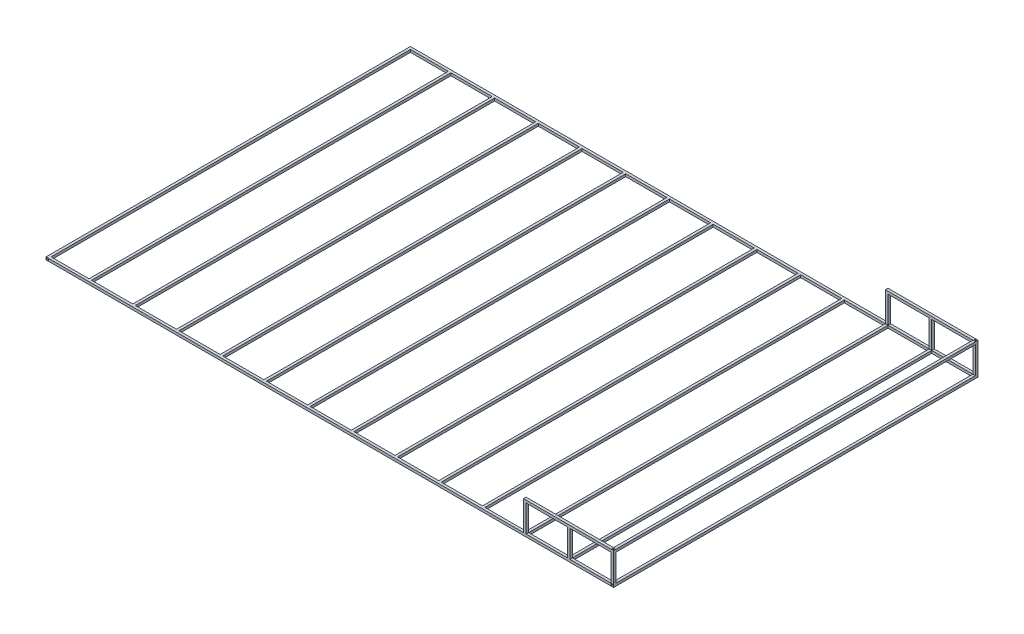
SolidWorks part; units mm, degrees
ref_plane "Front Plane" through (0, 0, 0) normal (0, 0, 1) x (1, 0, 0)
ref_plane "Top Plane" through (0, 0, 0) normal (0, 1, 0) x (1, 0, 0)
ref_plane "Right Plane" through (0, 0, 0) normal (1, 0, 0) x (0, 0, -1)
sketch "Sketch1" plane through (0, 0, 0) normal (0, 1, 0) x (1, 0, 0)
  line L1 (0, 0) -> (-8410, 0)
  line L2 (0, 0) -> (0, 5400)
  line L3 (0, 5400) -> (-8410, 5400)
  line L4 (-8410, 0) -> (-8410, 5400)
  point P5 (0, 0)
  point P6 (0, 0)
  dimension "D1" = 8410
  dimension "D2" = 5400
sketch "Sketch2" plane through (0, 0, 0) normal (0, 0, 1) x (1, 0, 0)
  line L0 (-35.4, 5.24) -> (-35.4, 32.86)
  line L1 (0, 0) -> (-38.1, 0)
  line L2 (0, 0) -> (0, 38.1)
  line L3 (0, 38.1) -> (-38.1, 38.1)
  line L4 (-38.1, 0) -> (-38.1, 38.1)
  line L5 (-5.24, 35.4) -> (-32.86, 35.4)
  line L6 (-2.7, 5.24) -> (-2.7, 32.86)
  line L7 (-5.24, 2.7) -> (-32.86, 2.7)
  line L8 (-35.4, 2.7) -> (-35.4, 35.4) construction
  line L9 (-2.7, 2.7) -> (-35.4, 2.7) construction
  line L10 (-2.7, 35.4) -> (-35.4, 35.4) construction
  line L11 (-2.7, 2.7) -> (-2.7, 35.4) construction
  arc A0 (-35.4, 5.24) -> (-32.86, 2.7) centre (-32.86, 5.24) ccw
  arc A1 (-35.4, 32.86) -> (-32.86, 35.4) centre (-32.86, 32.86) cw
  arc A2 (-5.24, 35.4) -> (-2.7, 32.86) centre (-5.24, 32.86) cw
  arc A3 (-2.7, 5.24) -> (-5.24, 2.7) centre (-5.24, 5.24) cw
  dimension "D4" = 2.54
  dimension "D1" = 38.1
  dimension "D2" = 38.1
  dimension "D3" = 2.7
extrude "Boss-Extrude1" add sketch "Sketch2" against normal up to vertex (5400 mm away) up to point (0, 0, -5400)
sketch "Sketch3" plane through (-38.1, 0, 0) normal (-1, 0, 0) x (0, 0, 1)
  line L0 (0, 0) -> (-5400, 0) construction
  line L1 (-5400, 38.1) -> (-5361.9, 38.1)
  line L2 (-5400, 38.1) -> (-5400, 0)
  line L3 (-5400, 0) -> (-5361.9, 0)
  line L4 (-5361.9, 38.1) -> (-5361.9, 0)
  line L5 (-5364.6, 32.86) -> (-5364.6, 5.24)
  line L6 (-5394.76, 2.7) -> (-5367.14, 2.7)
  line L7 (-5397.3, 32.86) -> (-5397.3, 5.24)
  line L8 (-5394.76, 35.4) -> (-5367.14, 35.4)
  line L9 (-5364.6, 35.4) -> (-5364.6, 2.7) construction
  line L10 (-5397.3, 2.7) -> (-5364.6, 2.7) construction
  line L11 (-5397.3, 35.4) -> (-5397.3, 2.7) construction
  line L12 (-5397.3, 35.4) -> (-5364.6, 35.4) construction
  line L14 (-2700, 254.2441) -> (-2700, -216.1397) construction
  line L15 (-5400, 38.1) -> (0, 38.1) construction
  line L16 (-2.7, 32.86) -> (-2.7, 5.24)
  line L17 (0, 38.1) -> (0, 0)
  line L18 (-5.24, 2.7) -> (-32.86, 2.7)
  line L19 (-5.24, 35.4) -> (-32.86, 35.4)
  line L20 (0, 38.1) -> (-38.1, 38.1)
  line L21 (0, 0) -> (-38.1, 0)
  line L22 (-35.4, 32.86) -> (-35.4, 5.24)
  line L23 (-38.1, 38.1) -> (-38.1, 0)
  arc A0 (-5364.6, 5.24) -> (-5367.14, 2.7) centre (-5367.14, 5.24) cw
  arc A1 (-5394.76, 2.7) -> (-5397.3, 5.24) centre (-5394.76, 5.24) cw
  arc A2 (-5397.3, 32.86) -> (-5394.76, 35.4) centre (-5394.76, 32.86) cw
  arc A3 (-5364.6, 32.86) -> (-5367.14, 35.4) centre (-5367.14, 32.86) ccw
  arc A4 (-2.7, 32.86) -> (-5.24, 35.4) centre (-5.24, 32.86) ccw
  arc A5 (-5.24, 2.7) -> (-2.7, 5.24) centre (-5.24, 5.24) ccw
  arc A6 (-35.4, 32.86) -> (-32.86, 35.4) centre (-32.86, 32.86) cw
  arc A7 (-35.4, 5.24) -> (-32.86, 2.7) centre (-32.86, 5.24) ccw
  point P25 (-2700, 38.1)
  dimension "D3" = 2.54
  dimension "D1" = 38.1
  dimension "D2" = 2.7
extrude "Boss-Extrude2" add sketch "Sketch3" along normal blind 8333.8
pattern_linear "LPattern1" count 2 spacing 8371.9 along (-1, 0, 0) of "Boss-Extrude1"
sketch "Sketch4" plane through (0, 0, -5361.9) normal (0, 0, 1) x (1, 0, 0)
  line L0 (-8371.9, 38.1) -> (-38.1, 38.1) construction
  line L1 (-647.7, 38.1) -> (-685.8, 38.1)
  line L2 (-647.7, 38.1) -> (-647.7, 0)
  line L3 (-647.7, 0) -> (-685.8, 0)
  line L4 (-685.8, 38.1) -> (-685.8, 0)
  line L5 (-8371.9, 0) -> (-38.1, 0) construction
  line L6 (-38.1, 0) -> (-38.1, 38.1) construction
  line L7 (-1295.4, 38.1) -> (-1295.4, 0)
  line L8 (-1333.5, 38.1) -> (-1333.5, 0)
  line L9 (-1295.4, 38.1) -> (-1333.5, 38.1)
  line L10 (-1295.4, 0) -> (-1333.5, 0)
  line L11 (-1943.1, 38.1) -> (-1943.1, 0)
  line L12 (-1981.2, 38.1) -> (-1981.2, 0)
  line L13 (-1943.1, 38.1) -> (-1981.2, 38.1)
  line L14 (-1943.1, 0) -> (-1981.2, 0)
  line L15 (-2590.8, 38.1) -> (-2590.8, 0)
  line L16 (-2628.9, 38.1) -> (-2628.9, 0)
  line L17 (-2590.8, 38.1) -> (-2628.9, 38.1)
  line L18 (-2590.8, 0) -> (-2628.9, 0)
  line L19 (-3238.5, 38.1) -> (-3238.5, 0)
  line L20 (-3276.6, 38.1) -> (-3276.6, 0)
  line L21 (-3238.5, 38.1) -> (-3276.6, 38.1)
  line L22 (-3238.5, 0) -> (-3276.6, 0)
  line L23 (-3886.2, 38.1) -> (-3886.2, 0)
  line L24 (-3924.3, 38.1) -> (-3924.3, 0)
  line L25 (-3886.2, 38.1) -> (-3924.3, 38.1)
  line L26 (-3886.2, 0) -> (-3924.3, 0)
  line L27 (-4533.9, 38.1) -> (-4533.9, 0)
  line L28 (-4572, 38.1) -> (-4572, 0)
  line L29 (-4533.9, 38.1) -> (-4572, 38.1)
  line L30 (-4533.9, 0) -> (-4572, 0)
  line L31 (-5181.6, 38.1) -> (-5181.6, 0)
  line L32 (-5219.7, 38.1) -> (-5219.7, 0)
  line L33 (-5181.6, 38.1) -> (-5219.7, 38.1)
  line L34 (-5181.6, 0) -> (-5219.7, 0)
  line L35 (-5829.3, 38.1) -> (-5829.3, 0)
  line L36 (-5867.4, 38.1) -> (-5867.4, 0)
  line L37 (-5829.3, 38.1) -> (-5867.4, 38.1)
  line L38 (-5829.3, 0) -> (-5867.4, 0)
  line L39 (-6477, 38.1) -> (-6477, 0)
  line L40 (-6515.1, 38.1) -> (-6515.1, 0)
  line L41 (-6477, 38.1) -> (-6515.1, 38.1)
  line L42 (-6477, 0) -> (-6515.1, 0)
  line L43 (-7124.7, 38.1) -> (-7124.7, 0)
  line L44 (-7162.8, 38.1) -> (-7162.8, 0)
  line L45 (-7124.7, 38.1) -> (-7162.8, 38.1)
  line L46 (-7124.7, 0) -> (-7162.8, 0)
  line L47 (-7772.4, 38.1) -> (-7772.4, 0)
  line L48 (-7810.5, 38.1) -> (-7810.5, 0)
  line L49 (-7772.4, 38.1) -> (-7810.5, 38.1)
  line L50 (-7772.4, 0) -> (-7810.5, 0)
  line L55 (-8420.1, 38.1) -> (-8458.2, 38.1) [skipped]
  line L56 (-8420.1, 0) -> (-8458.2, 0) [skipped]
  line L57 (-8458.2, 38.1) -> (-8458.2, 0) [skipped]
  line L58 (-8420.1, 38.1) -> (-8420.1, 0) [skipped]
  dimension "D1" = 38.1
  dimension "D2" = 609.6
  dimension "D4" = 609.6
  dimension "D3" = 13
extrude "Boss-Extrude3" add sketch "Sketch4" along normal up to surface (5323.8 mm away) up to face at (-4205, 19.05, -38.1)
sketch "Sketch5" plane through (0, 38.1, 0) normal (0, 1, 0) x (1, 0, 0)
  line L0 (-32.86, 35.4) -> (-5.24, 35.4)
  line L1 (-38.1, 38.1) -> (0, 38.1)
  line L2 (-38.1, 38.1) -> (-38.1, 0)
  line L3 (-38.1, 0) -> (0, 0)
  line L4 (0, 38.1) -> (0, 0)
  line L5 (-2.7, 32.86) -> (-2.7, 5.24)
  line L6 (-32.86, 2.7) -> (-5.24, 2.7)
  line L7 (-35.4, 32.86) -> (-35.4, 5.24)
  line L8 (-35.4, 35.4) -> (-2.7, 35.4) construction
  line L9 (-35.4, 35.4) -> (-35.4, 2.7) construction
  line L10 (-35.4, 2.7) -> (-2.7, 2.7) construction
  line L11 (-2.7, 35.4) -> (-2.7, 2.7) construction
  line L12 (0, 5400) -> (0, 0) construction
  line L13 (0, 2700) -> (-153.8549, 2700) construction
  line L14 (-35.4, 5367.14) -> (-35.4, 5394.76)
  line L15 (-32.86, 5397.3) -> (-5.24, 5397.3)
  line L16 (-2.7, 5367.14) -> (-2.7, 5394.76)
  line L17 (0, 5361.9) -> (0, 5400)
  line L18 (-38.1, 5400) -> (0, 5400)
  line L19 (-38.1, 5361.9) -> (-38.1, 5400)
  line L20 (-38.1, 5361.9) -> (0, 5361.9)
  line L21 (-32.86, 5364.6) -> (-5.24, 5364.6)
  line L22 (-680.56, 35.4) -> (-652.94, 35.4)
  line L23 (-683.1, 32.86) -> (-683.1, 5.24)
  line L24 (-680.56, 2.7) -> (-652.94, 2.7)
  line L25 (-650.4, 32.86) -> (-650.4, 5.24)
  line L26 (-685.8, 38.1) -> (-647.7, 38.1)
  line L27 (-647.7, 38.1) -> (-647.7, 0)
  line L28 (-685.8, 0) -> (-647.7, 0)
  line L29 (-685.8, 38.1) -> (-685.8, 0)
  line L30 (-685.8, 5361.9) -> (-685.8, 5400)
  line L31 (-683.1, 5367.14) -> (-683.1, 5394.76)
  line L32 (-680.56, 5364.6) -> (-652.94, 5364.6)
  line L33 (-685.8, 5361.9) -> (-647.7, 5361.9)
  line L34 (-650.4, 5367.14) -> (-650.4, 5394.76)
  line L35 (-647.7, 5361.9) -> (-647.7, 5400)
  line L36 (-685.8, 5400) -> (-647.7, 5400)
  line L37 (-680.56, 5397.3) -> (-652.94, 5397.3)
  line L38 (-1298.1, 32.86) -> (-1298.1, 5.24)
  line L39 (-1328.26, 2.7) -> (-1300.64, 2.7)
  line L40 (-1333.5, 0) -> (-1295.4, 0)
  line L41 (-1295.4, 38.1) -> (-1295.4, 0)
  line L42 (-1333.5, 38.1) -> (-1295.4, 38.1)
  line L43 (-1328.26, 35.4) -> (-1300.64, 35.4)
  line L44 (-1333.5, 38.1) -> (-1333.5, 0)
  line L45 (-1330.8, 32.86) -> (-1330.8, 5.24)
  line L46 (-1298.1, 5367.14) -> (-1298.1, 5394.76)
  line L47 (-1333.5, 5361.9) -> (-1295.4, 5361.9)
  line L48 (-1295.4, 5361.9) -> (-1295.4, 5400)
  line L49 (-1328.26, 5397.3) -> (-1300.64, 5397.3)
  line L50 (-1333.5, 5400) -> (-1295.4, 5400)
  line L51 (-1330.8, 5367.14) -> (-1330.8, 5394.76)
  line L52 (-1333.5, 5361.9) -> (-1333.5, 5400)
  line L53 (-1328.26, 5364.6) -> (-1300.64, 5364.6)
  line L54 (-1945.8, 32.86) -> (-1945.8, 5.24)
  line L55 (-1975.96, 2.7) -> (-1948.34, 2.7)
  line L56 (-1981.2, 0) -> (-1943.1, 0)
  line L57 (-1943.1, 38.1) -> (-1943.1, 0)
  line L58 (-1981.2, 38.1) -> (-1943.1, 38.1)
  line L59 (-1975.96, 35.4) -> (-1948.34, 35.4)
  line L60 (-1981.2, 38.1) -> (-1981.2, 0)
  line L61 (-1978.5, 32.86) -> (-1978.5, 5.24)
  line L62 (-1945.8, 5367.14) -> (-1945.8, 5394.76)
  line L63 (-1981.2, 5361.9) -> (-1943.1, 5361.9)
  line L64 (-1943.1, 5361.9) -> (-1943.1, 5400)
  line L65 (-1975.96, 5397.3) -> (-1948.34, 5397.3)
  line L66 (-1981.2, 5400) -> (-1943.1, 5400)
  line L67 (-1978.5, 5367.14) -> (-1978.5, 5394.76)
  line L68 (-1981.2, 5361.9) -> (-1981.2, 5400)
  line L69 (-1975.96, 5364.6) -> (-1948.34, 5364.6)
  line L70 (-2593.5, 32.86) -> (-2593.5, 5.24)
  line L71 (-2623.66, 2.7) -> (-2596.04, 2.7)
  line L72 (-2628.9, 0) -> (-2590.8, 0)
  line L73 (-2590.8, 38.1) -> (-2590.8, 0)
  line L74 (-2628.9, 38.1) -> (-2590.8, 38.1)
  line L75 (-2623.66, 35.4) -> (-2596.04, 35.4)
  line L76 (-2628.9, 38.1) -> (-2628.9, 0)
  line L77 (-2626.2, 32.86) -> (-2626.2, 5.24)
  line L78 (-2593.5, 5367.14) -> (-2593.5, 5394.76)
  line L79 (-2628.9, 5361.9) -> (-2590.8, 5361.9)
  line L80 (-2590.8, 5361.9) -> (-2590.8, 5400)
  line L81 (-2623.66, 5397.3) -> (-2596.04, 5397.3)
  line L82 (-2628.9, 5400) -> (-2590.8, 5400)
  line L83 (-2626.2, 5367.14) -> (-2626.2, 5394.76)
  line L84 (-2628.9, 5361.9) -> (-2628.9, 5400)
  line L85 (-2623.66, 5364.6) -> (-2596.04, 5364.6)
  line L86 (-3241.2, 32.86) -> (-3241.2, 5.24)
  line L87 (-3271.36, 2.7) -> (-3243.74, 2.7)
  line L88 (-3276.6, 0) -> (-3238.5, 0)
  line L89 (-3238.5, 38.1) -> (-3238.5, 0)
  line L90 (-3276.6, 38.1) -> (-3238.5, 38.1)
  line L91 (-3271.36, 35.4) -> (-3243.74, 35.4)
  line L92 (-3276.6, 38.1) -> (-3276.6, 0)
  line L93 (-3273.9, 32.86) -> (-3273.9, 5.24)
  line L94 (-3241.2, 5367.14) -> (-3241.2, 5394.76)
  line L95 (-3276.6, 5361.9) -> (-3238.5, 5361.9)
  line L96 (-3238.5, 5361.9) -> (-3238.5, 5400)
  line L97 (-3271.36, 5397.3) -> (-3243.74, 5397.3)
  line L98 (-3276.6, 5400) -> (-3238.5, 5400)
  line L99 (-3273.9, 5367.14) -> (-3273.9, 5394.76)
  line L100 (-3276.6, 5361.9) -> (-3276.6, 5400)
  line L101 (-3271.36, 5364.6) -> (-3243.74, 5364.6)
  line L102 (-3888.9, 32.86) -> (-3888.9, 5.24)
  line L103 (-3919.06, 2.7) -> (-3891.44, 2.7)
  line L104 (-3924.3, 0) -> (-3886.2, 0)
  line L105 (-3886.2, 38.1) -> (-3886.2, 0)
  line L106 (-3924.3, 38.1) -> (-3886.2, 38.1)
  line L107 (-3919.06, 35.4) -> (-3891.44, 35.4)
  line L108 (-3924.3, 38.1) -> (-3924.3, 0)
  line L109 (-3921.6, 32.86) -> (-3921.6, 5.24)
  line L110 (-3888.9, 5367.14) -> (-3888.9, 5394.76)
  line L111 (-3924.3, 5361.9) -> (-3886.2, 5361.9)
  line L112 (-3886.2, 5361.9) -> (-3886.2, 5400)
  line L113 (-3919.06, 5397.3) -> (-3891.44, 5397.3)
  line L114 (-3924.3, 5400) -> (-3886.2, 5400)
  line L115 (-3921.6, 5367.14) -> (-3921.6, 5394.76)
  line L116 (-3924.3, 5361.9) -> (-3924.3, 5400)
  line L117 (-3919.06, 5364.6) -> (-3891.44, 5364.6)
  line L118 (-647.7, 38.1) -> (-647.7, 5361.9) construction
  line L119 (-647.7, 5361.9) -> (-38.1, 5361.9) construction
  line L120 (-1333.5, 38.1) -> (-1333.5, 5361.9) construction
  line L121 (-1943.1, 5361.9) -> (-1333.5, 5361.9) construction
  arc A0 (-32.86, 35.4) -> (-35.4, 32.86) centre (-32.86, 32.86) ccw
  arc A1 (-32.86, 2.7) -> (-35.4, 5.24) centre (-32.86, 5.24) cw
  arc A2 (-2.7, 5.24) -> (-5.24, 2.7) centre (-5.24, 5.24) cw
  arc A3 (-5.24, 35.4) -> (-2.7, 32.86) centre (-5.24, 32.86) cw
  arc A4 (-5.24, 5364.6) -> (-2.7, 5367.14) centre (-5.24, 5367.14) ccw
  arc A5 (-2.7, 5394.76) -> (-5.24, 5397.3) centre (-5.24, 5394.76) ccw
  arc A6 (-32.86, 5397.3) -> (-35.4, 5394.76) centre (-32.86, 5394.76) ccw
  arc A7 (-32.86, 5364.6) -> (-35.4, 5367.14) centre (-32.86, 5367.14) cw
  arc A8 (-680.56, 35.4) -> (-683.1, 32.86) centre (-680.56, 32.86) ccw
  arc A9 (-680.56, 2.7) -> (-683.1, 5.24) centre (-680.56, 5.24) cw
  arc A10 (-650.4, 5.24) -> (-652.94, 2.7) centre (-652.94, 5.24) cw
  arc A11 (-652.94, 35.4) -> (-650.4, 32.86) centre (-652.94, 32.86) cw
  arc A12 (-680.56, 5364.6) -> (-683.1, 5367.14) centre (-680.56, 5367.14) cw
  arc A13 (-652.94, 5364.6) -> (-650.4, 5367.14) centre (-652.94, 5367.14) ccw
  arc A14 (-650.4, 5394.76) -> (-652.94, 5397.3) centre (-652.94, 5394.76) ccw
  arc A15 (-680.56, 5397.3) -> (-683.1, 5394.76) centre (-680.56, 5394.76) ccw
  arc A16 (-1298.1, 5.24) -> (-1300.64, 2.7) centre (-1300.64, 5.24) cw
  arc A17 (-1300.64, 35.4) -> (-1298.1, 32.86) centre (-1300.64, 32.86) cw
  arc A18 (-1328.26, 35.4) -> (-1330.8, 32.86) centre (-1328.26, 32.86) ccw
  arc A19 (-1328.26, 2.7) -> (-1330.8, 5.24) centre (-1328.26, 5.24) cw
  arc A20 (-1300.64, 5364.6) -> (-1298.1, 5367.14) centre (-1300.64, 5367.14) ccw
  arc A21 (-1298.1, 5394.76) -> (-1300.64, 5397.3) centre (-1300.64, 5394.76) ccw
  arc A22 (-1328.26, 5397.3) -> (-1330.8, 5394.76) centre (-1328.26, 5394.76) ccw
  arc A23 (-1328.26, 5364.6) -> (-1330.8, 5367.14) centre (-1328.26, 5367.14) cw
  arc A24 (-1945.8, 5.24) -> (-1948.34, 2.7) centre (-1948.34, 5.24) cw
  arc A25 (-1948.34, 35.4) -> (-1945.8, 32.86) centre (-1948.34, 32.86) cw
  arc A26 (-1975.96, 35.4) -> (-1978.5, 32.86) centre (-1975.96, 32.86) ccw
  arc A27 (-1975.96, 2.7) -> (-1978.5, 5.24) centre (-1975.96, 5.24) cw
  arc A28 (-1948.34, 5364.6) -> (-1945.8, 5367.14) centre (-1948.34, 5367.14) ccw
  arc A29 (-1945.8, 5394.76) -> (-1948.34, 5397.3) centre (-1948.34, 5394.76) ccw
  arc A30 (-1975.96, 5397.3) -> (-1978.5, 5394.76) centre (-1975.96, 5394.76) ccw
  arc A31 (-1975.96, 5364.6) -> (-1978.5, 5367.14) centre (-1975.96, 5367.14) cw
  arc A32 (-2593.5, 5.24) -> (-2596.04, 2.7) centre (-2596.04, 5.24) cw
  arc A33 (-2596.04, 35.4) -> (-2593.5, 32.86) centre (-2596.04, 32.86) cw
  arc A34 (-2623.66, 35.4) -> (-2626.2, 32.86) centre (-2623.66, 32.86) ccw
  arc A35 (-2623.66, 2.7) -> (-2626.2, 5.24) centre (-2623.66, 5.24) cw
  arc A36 (-2596.04, 5364.6) -> (-2593.5, 5367.14) centre (-2596.04, 5367.14) ccw
  arc A37 (-2593.5, 5394.76) -> (-2596.04, 5397.3) centre (-2596.04, 5394.76) ccw
  arc A38 (-2623.66, 5397.3) -> (-2626.2, 5394.76) centre (-2623.66, 5394.76) ccw
  arc A39 (-2623.66, 5364.6) -> (-2626.2, 5367.14) centre (-2623.66, 5367.14) cw
  arc A40 (-3241.2, 5.24) -> (-3243.74, 2.7) centre (-3243.74, 5.24) cw
  arc A41 (-3243.74, 35.4) -> (-3241.2, 32.86) centre (-3243.74, 32.86) cw
  arc A42 (-3271.36, 35.4) -> (-3273.9, 32.86) centre (-3271.36, 32.86) ccw
  arc A43 (-3271.36, 2.7) -> (-3273.9, 5.24) centre (-3271.36, 5.24) cw
  arc A44 (-3243.74, 5364.6) -> (-3241.2, 5367.14) centre (-3243.74, 5367.14) ccw
  arc A45 (-3241.2, 5394.76) -> (-3243.74, 5397.3) centre (-3243.74, 5394.76) ccw
  arc A46 (-3271.36, 5397.3) -> (-3273.9, 5394.76) centre (-3271.36, 5394.76) ccw
  arc A47 (-3271.36, 5364.6) -> (-3273.9, 5367.14) centre (-3271.36, 5367.14) cw
  arc A48 (-3888.9, 5.24) -> (-3891.44, 2.7) centre (-3891.44, 5.24) cw
  arc A49 (-3891.44, 35.4) -> (-3888.9, 32.86) centre (-3891.44, 32.86) cw
  arc A50 (-3919.06, 35.4) -> (-3921.6, 32.86) centre (-3919.06, 32.86) ccw
  arc A51 (-3919.06, 2.7) -> (-3921.6, 5.24) centre (-3919.06, 5.24) cw
  arc A52 (-3891.44, 5364.6) -> (-3888.9, 5367.14) centre (-3891.44, 5367.14) ccw
  arc A53 (-3888.9, 5394.76) -> (-3891.44, 5397.3) centre (-3891.44, 5394.76) ccw
  arc A54 (-3919.06, 5397.3) -> (-3921.6, 5394.76) centre (-3919.06, 5394.76) ccw
  arc A55 (-3919.06, 5364.6) -> (-3921.6, 5367.14) centre (-3919.06, 5367.14) cw
  dimension "D2" = 2.54
  dimension "D1" = 2.7
  dimension "D3" = 2
  dimension "D4" = 6
extrude "Boss-Extrude4" add sketch "Sketch5" along normal blind 435.864 contours L4 L1 L2 L3 L0 A3 L5 A2 L6 A1 L7 A0 | L19 L20 L17 L18 L21 A7 L14 A6 L15 A5 L16 A4 region at (-19.05, 38.1, -37.5612) region at (-19.05, 38.1, -5362.4388)
sketch "Sketch6" plane through (0, 0, -5361.9) normal (0, 0, 1) x (1, 0, 0)
  line L0 (-38.1, 473.964) -> (-38.1, 38.1) construction
  line L1 (0, 473.964) -> (-38.1, 473.964)
  line L2 (0, 473.964) -> (0, 435.864)
  line L3 (0, 435.864) -> (-38.1, 435.864)
  line L4 (-38.1, 473.964) -> (-38.1, 435.864)
  line L5 (-5.24, 438.564) -> (-32.86, 438.564)
  line L6 (-35.4, 468.724) -> (-35.4, 441.104)
  line L7 (-5.24, 471.264) -> (-32.86, 471.264)
  line L8 (-2.7, 468.724) -> (-2.7, 441.104)
  line L9 (-35.4, 471.264) -> (-35.4, 438.564) construction
  line L10 (-2.7, 471.264) -> (-35.4, 471.264) construction
  line L11 (-2.7, 438.564) -> (-35.4, 438.564) construction
  line L12 (-2.7, 471.264) -> (-2.7, 438.564) construction
  arc A0 (-35.4, 468.724) -> (-32.86, 471.264) centre (-32.86, 468.724) cw
  arc A1 (-32.86, 438.564) -> (-35.4, 441.104) centre (-32.86, 441.104) cw
  arc A2 (-5.24, 438.564) -> (-2.7, 441.104) centre (-5.24, 441.104) ccw
  arc A3 (-5.24, 471.264) -> (-2.7, 468.724) centre (-5.24, 468.724) cw
  dimension "D3" = 2.54
  dimension "D1" = 38.1
  dimension "D2" = 2.7
extrude "Boss-Extrude5" add sketch "Sketch6" along normal up to surface (5323.8 mm away) up to face at (-19.05, 256.032, -38.1)
extrude "Boss-Extrude6" add sketch "Sketch5<3>" along normal blind 397.764 contours L36 L30 L33 L35 A15 L37 A14 L34 A13 L32 A12 L31 | L26 L29 L28 L27 L22 A11 L25 A10 L24 A9 L23 A8 | L42 L44 L40 L41 L39 A19 L45 A18 L43 A17 L38 A16 | L52 L47 L48 L50 L53 A23 L51 A22 L49 A21 L46 A20 region at (-666.75, 38.1, -37.5612) region at (-685.2612, 38.1, -5380.95) region at (-1332.9612, 38.1, -19.05) region at (-1332.9612, 38.1, -5380.95)
sketch "Sketch5<3>" plane through (0, 38.1, 0) normal (0, 1, 0) x (1, 0, 0) same geometry as "Sketch5"
sketch "Sketch7" plane through (-38.1, 0, 0) normal (-1, 0, 0) x (0, 0, 1)
  line L0 (-35.4, 441.104) -> (-35.4, 468.724)
  line L1 (-38.1, 435.864) -> (0, 435.864)
  line L2 (-38.1, 435.864) -> (-38.1, 473.964)
  line L3 (-38.1, 473.964) -> (0, 473.964)
  line L4 (0, 435.864) -> (0, 473.964)
  line L5 (-32.86, 471.264) -> (-5.24, 471.264)
  line L6 (-2.7, 441.104) -> (-2.7, 468.724)
  line L7 (-32.86, 438.564) -> (-5.24, 438.564)
  line L8 (-35.4, 438.564) -> (-35.4, 471.264) construction
  line L9 (-35.4, 438.564) -> (-2.7, 438.564) construction
  line L10 (-2.7, 438.564) -> (-2.7, 471.264) construction
  line L11 (-35.4, 471.264) -> (-2.7, 471.264) construction
  line L12 (-2700, 473.964) -> (-2700, 209.2227) construction
  line L13 (-5400, 473.964) -> (0, 473.964) construction
  line L14 (-5367.14, 438.564) -> (-5394.76, 438.564)
  line L15 (-5397.3, 441.104) -> (-5397.3, 468.724)
  line L16 (-5367.14, 471.264) -> (-5394.76, 471.264)
  line L17 (-5400, 435.864) -> (-5400, 473.964)
  line L18 (-5361.9, 473.964) -> (-5400, 473.964)
  line L19 (-5361.9, 435.864) -> (-5361.9, 473.964)
  line L20 (-5361.9, 435.864) -> (-5400, 435.864)
  line L21 (-5364.6, 441.104) -> (-5364.6, 468.724)
  arc A0 (-35.4, 441.104) -> (-32.86, 438.564) centre (-32.86, 441.104) ccw
  arc A1 (-2.7, 441.104) -> (-5.24, 438.564) centre (-5.24, 441.104) cw
  arc A2 (-5.24, 471.264) -> (-2.7, 468.724) centre (-5.24, 468.724) cw
  arc A3 (-35.4, 468.724) -> (-32.86, 471.264) centre (-32.86, 468.724) cw
  arc A4 (-5364.6, 468.724) -> (-5367.14, 471.264) centre (-5367.14, 468.724) ccw
  arc A5 (-5394.76, 471.264) -> (-5397.3, 468.724) centre (-5394.76, 468.724) ccw
  arc A6 (-5397.3, 441.104) -> (-5394.76, 438.564) centre (-5394.76, 441.104) ccw
  arc A7 (-5364.6, 441.104) -> (-5367.14, 438.564) centre (-5367.14, 441.104) cw
  dimension "D2" = 2.54
  dimension "D1" = 2.7
extrude "Boss-Extrude7" add sketch "Sketch7" along normal up to surface (1295.4 mm away) up to face at (-1333.5, 236.982, -5380.95)
equation "\"D2@Sketch2\"=\"D1@Sketch2\""
